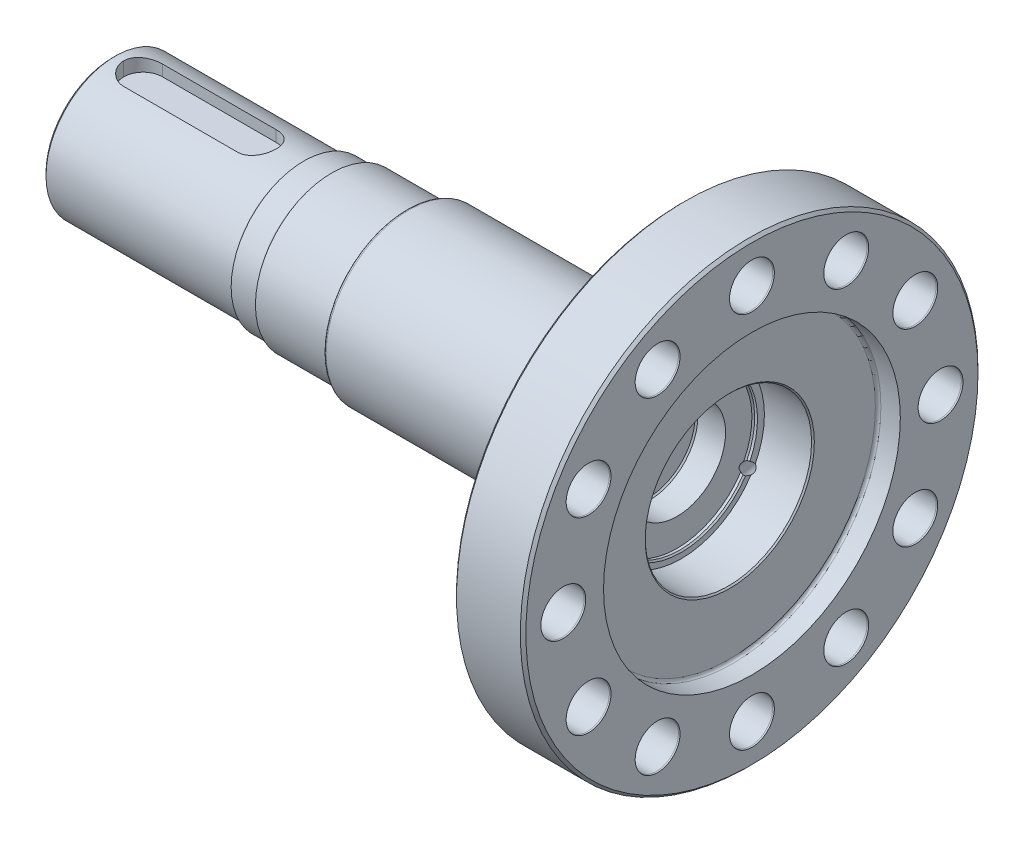
SolidWorks part; units mm, degrees
ref_plane "前视基准面" through (0, 0, 0) normal (0, 0, 1) x (1, 0, 0)
ref_plane "上视基准面" through (0, 0, 0) normal (0, 1, 0) x (1, 0, 0)
ref_plane "右视基准面" through (0, 0, 0) normal (1, 0, 0) x (0, 0, -1)
sketch "草图2" plane through (0, 0, 0) normal (1, 0, 0) x (0, 0, -1)
  circle A0 centre (0, 0) radius 165
  dimension "D1" = 330
extrude "凸台-拉伸1" add sketch "草图2" against normal blind 50
sketch "草图5" plane through (-50, 0, 0) normal (-1, 0, 0) x (0, 0, 1)
  circle A0 centre (0, 0) radius 110
  dimension "D1" = 220
extrude "凸台-拉伸2" add sketch "草图5" along normal blind 55 draft 30 contours A0
sketch "草图7" plane through (-105, 0, 0) normal (-1, 0, 0) x (0, 0, 1)
  circle A0 centre (0, 0) radius 60
  dimension "D1" = 120
extrude "凸台-拉伸3" add sketch "草图7" along normal blind 144
sketch "草图8" plane through (-249, 0, 0) normal (-1, 0, 0) x (0, 0, 1)
  circle A0 centre (0, 0) radius 55
  dimension "D1" = 110
extrude "凸台-拉伸4" add sketch "草图8" along normal blind 54
sketch "草图9" plane through (-303, 0, 0) normal (-1, 0, 0) x (0, 0, 1)
  circle A0 centre (0, 0) radius 52.5
  dimension "D1" = 105
extrude "undef" add sketch "草图9" along normal blind 20
sketch "草图10" plane through (-323, 0, 0) normal (-1, 0, 0) x (0, 0, 1)
  circle A0 centre (0, 0) radius 50
  dimension "D1" = 100
extrude "凸台-拉伸6" add sketch "草图10" along normal blind 138
sketch "草图11" plane through (-461, 0, 0) normal (-1, 0, 0) x (0, 0, 1)
  line L0 (-14, 48) -> (-14, 40)
  line L1 (-14, 40) -> (14, 40)
  line L2 (0, 40) -> (0, 5.4939) construction
  line L3 (14, 48) -> (14, 40)
  arc A0 (-14, 48) -> (14, 48) centre (0, 0) ccw construction
  circle A1 centre (0, 0) radius 50
  arc A2 (14, 48) -> (-14, 48) centre (0, 0) ccw
  point P10 (0, -50)
  dimension "D2" = 90
  dimension "D3" = 28
  dimension "D1" = 0
extrude "切除-拉伸1" cut sketch "草图11" against normal blind 110 from offset 8 offset against normal yes
fillet "圆角1" radius 14 4 edges at (-343, 44, -14) (-453, 44, 14) (-343, 44, 14) (-453, 44, -14)
sketch "草图12" plane through (0, 0, 0) normal (0, 1, 0) x (1, 0, 0)
  line L1 (-461, 17) -> (-459.8453, 15)
  line L2 (-461, 50) -> (-461, -50) construction
  line L3 (-459.8453, 15) -> (-445.1229, 6.5)
  line L4 (-445.1229, 6.5) -> (-445.1229, 0)
  line L5 (-461, 17) -> (-461, 0)
  line L8 (-461, 0) -> (-445.1229, 0)
  point P10 (-461, 8.5)
  point P11 (-445.1229, 3.25)
  point P16 (-461, 0)
  point P17 (-445.1229, 0)
revolve "切除-旋转2" cut sketch "草图12" angle 360 about L8
sketch "草图15" plane through (-461, 0, 0) normal (-1, 0, 0) x (0, 0, 1)
  point P0 (0, 0)
hole_wizard "M12 螺纹孔2" positions "草图15" profile "草图16" tap size "M12" standard "GB"
sketch "草图16" plane through (-461, 0, 0) normal (0, 1, 0) x (0, 0, 1)
  line L0 (0, 0) -> (0, 40)
  line L1 (0, 40) -> (5.1, 36.9356)
  line L2 (5.1, 36.9356) -> (5.1, 0)
  line L5 (5.1, 0) -> (0, 0)
  line L10 (0, 40) -> (-5.1, 36.9356) construction
  line L11 (0, -6.35) -> (0, 107.95) construction
  dimension "螺纹孔钻头直径" = 10.2
  dimension "螺纹孔钻头深度" = 40
  dimension "导头角度" = 118
cosmetic thread "孔螺纹线2" parameters "D1"=36, "D2"=12
sketch "草图17" plane through (0, 0, 0) normal (1, 0, 0) x (0, 0, -1)
  circle A0 centre (0, 0) radius 107
  dimension "D1" = 214
extrude "切除-拉伸2" cut sketch "草图17" against normal blind 16
sketch "草图18" plane through (-16, 0, 0) normal (1, 0, 0) x (0, 0, -1)
  circle A0 centre (0, 0) radius 60
  dimension "D1" = 120
extrude "切除-拉伸3" cut sketch "草图18" against normal blind 35
sketch "草图19" plane through (-51, 0, 0) normal (1, 0, 0) x (0, 0, -1)
  circle A0 centre (0, 0) radius 55
  dimension "D1" = 110
extrude "切除-拉伸4" cut sketch "草图19" against normal blind 3
sketch "草图20" plane through (-54, 0, 0) normal (1, 0, 0) x (0, 0, -1)
  circle A0 centre (0, 0) radius 35
  dimension "D1" = 70
extrude "切除-拉伸5" cut sketch "草图20" against normal blind 21
sketch "草图21" plane through (0, 0, 0) normal (1, 0, 0) x (0, 0, -1)
  circle A0 centre (0, 0) radius 136 construction
  circle A1 centre (0, -136) radius 16
  dimension "D1" = 272
  dimension "D2" = 16
extrude "切除-拉伸6" cut sketch "草图21" against normal up to next
chamfer "倒角1" distance 1 angle 10 1 edges at (0, -136, -16) first distance on face at (0, -136, -16)
pattern_circular "阵列(圆周)1" count 12 over 360 about axis through (0, 0, 0) along (1, 0, 0) of "倒角1", "切除-拉伸6"
ref_plane "基准面5" through (-60.1314, 104.1506, 0) normal (-0.5, 0.866, 0) x (0.866, 0.5, 0)
sketch "草图22" plane through (-60.1314, 104.1506, 0) normal (-0.5, 0.866, 0) x (0.866, 0.5, 0)
  circle A0 centre (-16.8098, 0) radius 4
  ellipse E0 centre (-90.9327, 0) end of major axis (-90.9327, 78.2457) minor radius 39.1229 construction
  point P8 (-51.8098, 0)
  dimension "D1" = 8
  dimension "D2" = 35
extrude "切除-拉伸7" cut sketch "草图22" against normal up to next
pattern_circular "阵列(圆周)2" count 3 over 360 about axis through (-50, 0, 0) along (1, 0, 0) of "切除-拉伸7"
chamfer "倒角2" distance 2 angle 45 3 edges at (-461, 0, 50) (-50, 0, -165) (0, 0, -165)
fillet "圆角2" radius 2 5 edges at (-105, 0, 60) (-249, 0, 60) (-249, 0, 55) (-303, 0, 52.5) (-323, 0, 50)
chamfer "倒角3" distance 1 angle 45 5 edges at (-75, 0, -35) (-16, 0, -60) (-51, -55, 0) (-54, 27.5, -47.6314) (-51, 27.5, 47.6314)
fillet "圆角3" radius 2 1 edges at (-16, 0, -107)
